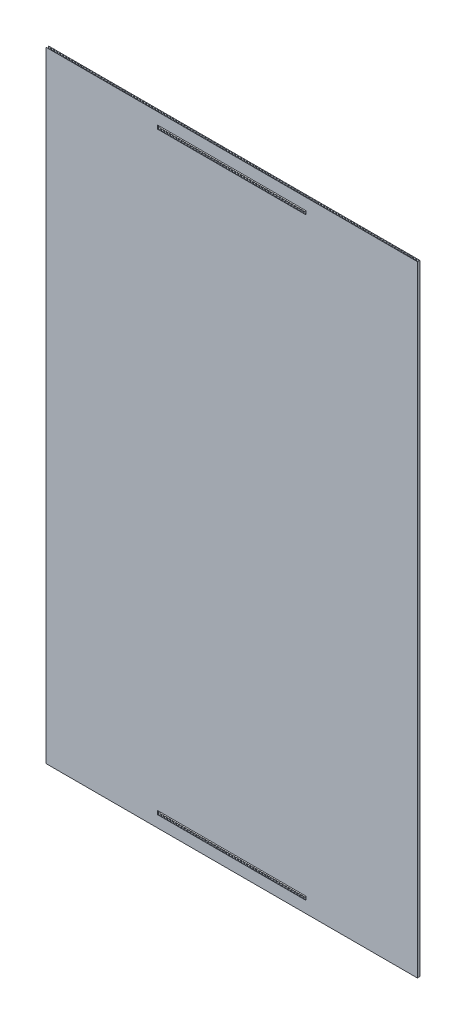
SolidWorks part; units mm, degrees
material "Acrylic (Medium-high impact)"
ref_plane "Front Plane" through (0, 0, 0) normal (0, 0, 1) x (1, 0, 0)
ref_plane "Top Plane" through (0, 0, 0) normal (0, 1, 0) x (1, 0, 0)
ref_plane "Right Plane" through (0, 0, 0) normal (1, 0, 0) x (0, 0, -1)
sketch "Sketch1" plane through (0, 0, 0) normal (0, 1, 0) x (1, 0, 0)
  line L0 (5, -4) -> (-5.3, -4)
  line L1 (-5.3, -4) -> (5, -4) construction
  line L2 (-5, -4) -> (-5, 4) construction
  line L3 (-5.3, 4) -> (5, 4) construction
  line L4 (5, -4) -> (5, 4) construction
  line L5 (-5, -4) -> (5, 4) construction
  line L6 (-5, 4) -> (5, -4) construction
  line L7 (4.7, -3.7) -> (4.7, 3.7)
  line L8 (-5.3, 3.7) -> (4.7, 3.7)
  line L9 (-5.3, -3.7) -> (4.7, -3.7)
  line L10 (5, 4) -> (5, -4)
  line L11 (-5, 4) -> (5, 4) construction
  line L12 (-5, 3.7) -> (5, 3.7) construction
  line L13 (-5, -3.7) -> (5, -3.7) construction
  line L14 (-5, -4) -> (5, -4) construction
  line L15 (5, 4) -> (-5.3, 4)
  line L16 (-5.3, 4) -> (-5.3, -4) construction
  line L17 (-5.3, 4) -> (-5.3, 3.7)
  line L18 (4.7, -4) -> (4.7, 4) construction
  line L19 (-5.3, -3.7) -> (-5.3, -4)
  point P0 (0, 0)
  dimension "D1" = 8
  dimension "D2" = 10
  dimension "D6" = 0.3
  dimension "D3" = 0.3
  dimension "D4" = 0.3
  dimension "D5" = 0.3
extrude "Boss-Extrude1" add sketch "Sketch1" along normal blind 2090
pattern_linear "LPattern1" count 125 spacing 10 along (1, 0, 0) of "Boss-Extrude1"
sketch "Sketch2" plane through (0, 0, 4) normal (0, 0, 1) x (1, 0, 0)
  line L0 (1245, 45) -> (-5.3, 45) construction
  line L1 (1245, 2090) -> (1245, 0) construction
  line L2 (-5.3, 2090) -> (-5.3, 0) construction
  line L3 (-5.3, 0) -> (1245, 0) construction
  line L4 (1245, 51) -> (-5.3, 51) construction
  line L5 (1245, 38.9) -> (-5.3, 38.9) construction
  line L6 (619.85, 38.9) -> (619.85, 51) construction
  line L7 (869.95, 38.9) -> (869.95, 51)
  line L8 (369.75, 38.9) -> (369.75, 51)
  line L9 (369.75, 51) -> (869.95, 51)
  line L10 (869.95, 38.9) -> (369.75, 38.9)
  line L12 (1245, 51) -> (-5.3, 51) construction
  line L13 (1245, 45) -> (-5.3, 45) construction
  dimension "D1" = 45
  dimension "D2" = 6
  dimension "D3" = 12.1
  dimension "D4" = 250.1
  dimension "D5" = 250.1
extrude "Cut-Extrude1" cut sketch "Sketch2" against normal through all
pattern_linear "LPattern2" count 2 spacing 2000 along (0, 1, 0) of "Cut-Extrude1"
